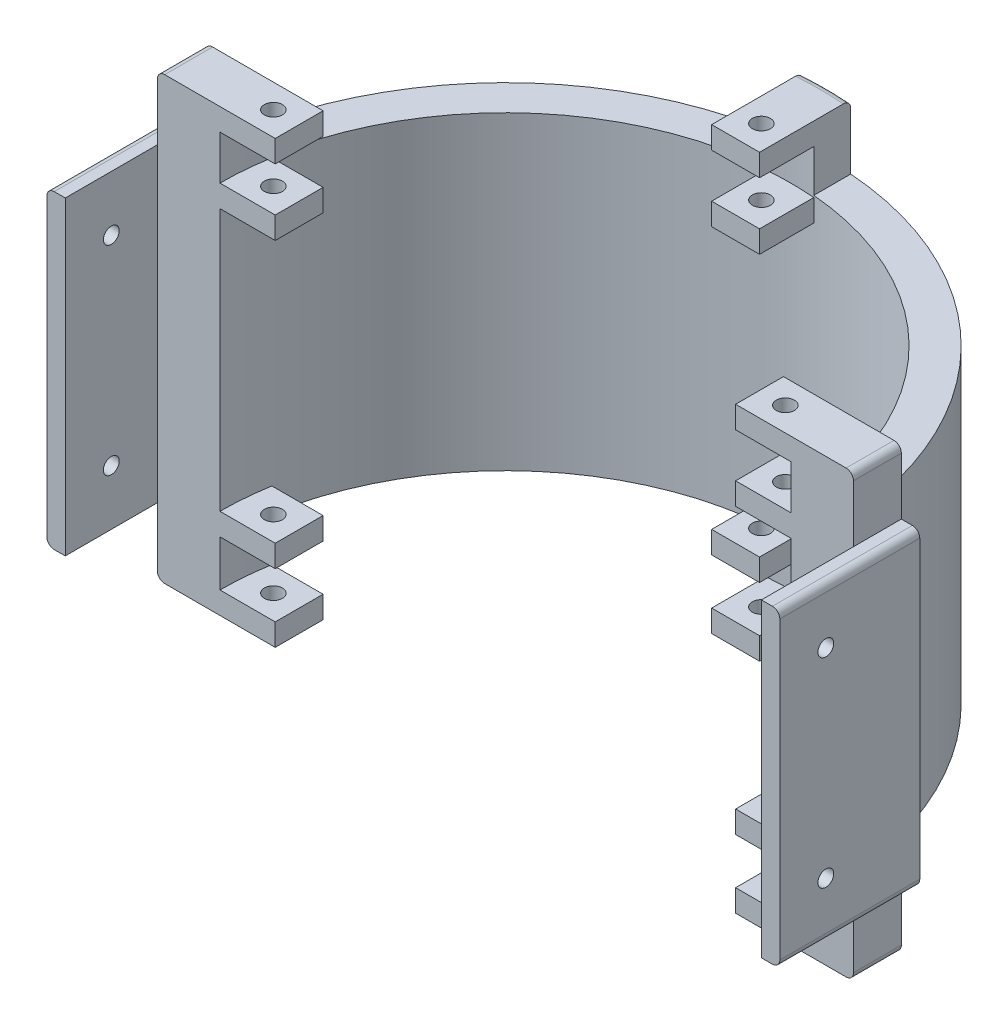
SolidWorks part; units mm, degrees
ref_plane "Front Plane" through (0, 0, 0) normal (0, 0, 1) x (1, 0, 0)
ref_plane "Top Plane" through (0, 0, 0) normal (0, 1, 0) x (1, 0, 0)
ref_plane "Right Plane" through (0, 0, 0) normal (1, 0, 0) x (0, 0, -1)
sketch "Sketch1" plane through (0, 0, 0) normal (0, 1, 0) x (1, 0, 0)
  line L0 (-148.0369, 0) -> (-77.5, 0) construction
  line L1 (-86.5289, 13) -> (-99.5, 13)
  line L2 (-99.5, 13) -> (-99.5, -25)
  line L3 (-99.5, -25) -> (-94.5, -25)
  line L4 (-94.5, -25) -> (-94.5, 0)
  line L5 (-94.5, 0) -> (-77.5, 0)
  line L7 (99.5, -25) -> (99.5, 13)
  line L8 (-65.0144, 0) -> (144.5537, 0) construction
  line L9 (99.5, 13) -> (86.5289, 13)
  line L10 (77.5, 0) -> (94.5, 0)
  line L11 (94.5, 0) -> (94.5, -25)
  line L12 (94.5, -25) -> (99.5, -25)
  arc A0 (77.5, 0) -> (-77.5, 0) centre (0, 0) ccw
  arc A1 (-86.5289, 13) -> (86.5289, 13) centre (0, 0) cw
  dimension "D1" = 155
  dimension "D4" = 10
  dimension "D2" = 25
  dimension "D3" = 25
  dimension "D5" = 17
  dimension "D6" = 17
  dimension "D7" = 5
  dimension "D8" = 5
  dimension "D9" = 13
  dimension "D10" = 13
extrude "Boss-Extrude1" add sketch "Sketch1" along normal blind 84.17
sketch "Sketch3" plane through (0, 84.17, 0) normal (0, 1, 0) x (1, 0, 0)
  line L0 (-94.5, 0) -> (-62.5, 0)
  line L1 (-94.5, 0) -> (-77.5, 0) construction
  line L2 (-62.5, 0) -> (-62.5, 13)
  line L3 (-62.5, 13) -> (-94.5, 13)
  line L5 (-94.5, 13) -> (-94.5, 0)
  line L6 (94.5, 0) -> (62.5, 0)
  line L7 (77.5, 0) -> (94.5, 0) construction
  line L8 (62.5, 0) -> (62.5, 13)
  line L9 (62.5, 13) -> (94.5, 13)
  line L11 (94.5, 13) -> (94.5, 0)
  line L12 (-94.5, -25) -> (-94.5, 0) construction
  line L13 (94.5, 0) -> (94.5, -25) construction
  dimension "D1" = 32
  dimension "D2" = 32
extrude "Boss-Extrude2" add sketch "Sketch3" against normal blind 6 from offset 0.5 offset against normal yes
sketch "Sketch4" plane through (0, 84.17, 0) normal (0, 1, 0) x (1, 0, 0)
  line L0 (-94.5, 13) -> (-76.4019, 13)
  line L1 (-94.5, 0) -> (-77.5, 0)
  line L2 (76.4019, 13) -> (94.5, 13)
  line L3 (94.5, 0) -> (77.5, 0)
  line L4 (-94.5, 0) -> (-94.5, 13)
  line L5 (99.5, 13) -> (86.5289, 13) construction
  line L6 (77.5, 0) -> (94.5, 0) construction
  line L7 (94.5, 13) -> (94.5, 0)
  line L8 (-94.5, -25) -> (-94.5, 0) construction
  line L9 (94.5, 0) -> (94.5, -25) construction
  arc A6 (-76.4019, 13) -> (-77.5, 0) centre (0, 0) ccw
  arc A7 (77.5, 0) -> (76.4019, 13) centre (0, 0) ccw
extrude "Boss-Extrude3" add sketch "Sketch4" along normal blind 11.5
sketch "Sketch5" plane through (0, 95.67, 0) normal (0, 1, 0) x (1, 0, 0)
  line L1 (-94.5, 0) -> (-62.5, 0)
  line L2 (-94.5, 0) -> (-94.5, 13)
  line L3 (-94.5, 13) -> (-62.5, 13)
  line L4 (-62.5, 0) -> (-62.5, 13)
  line L5 (94.5, 13) -> (62.5, 13)
  line L6 (94.5, 13) -> (94.5, 0)
  line L7 (94.5, 0) -> (62.5, 0)
  line L8 (62.5, 13) -> (62.5, 0)
extrude "Boss-Extrude4" add sketch "Sketch5" along normal blind 6
sketch "Sketch7" plane through (-99.5, 0, 0) normal (-1, 0, 0) x (0, 0, 1)
  line L0 (-13, 84.17) -> (25, 84.17) construction
  line L1 (-13, 0) -> (25, 0) construction
  line L2 (25, 84.17) -> (25, 0) construction
  circle A0 centre (12.5, 69.17) radius 2.15
  circle A1 centre (12.5, 15) radius 2.15
  dimension "D1" = 4.3
  dimension "D2" = 4.3
  dimension "D3" = 15
  dimension "D4" = 15
  dimension "D5" = 12.5
  dimension "D6" = 12.5
extrude "Cut-Extrude1" cut sketch "Sketch7" against normal through all
sketch "Sketch9" plane through (0, 0, 0) normal (0, -1, 0) x (1, 0, 0)
  line L0 (-86.5289, -13) -> (-99.5, -13) construction
  line L1 (-93.0144, -13) -> (-62.5, -13)
  line L2 (-93.0144, -13) -> (-93.0144, 0)
  line L3 (-93.0144, 0) -> (-62.5, 0)
  line L4 (-62.5, -13) -> (-62.5, 0)
  line L5 (99.5, -13) -> (86.5289, -13) construction
  line L6 (93.0144, -13) -> (62.5, -13)
  line L7 (93.0144, -13) -> (93.0144, 0)
  line L8 (93.0144, 0) -> (62.5, 0)
  line L9 (62.5, -13) -> (62.5, 0)
extrude "Boss-Extrude5" add sketch "Sketch9" against normal blind 6 from offset 0.5 offset against normal yes
sketch "Sketch11" plane through (0, 0, 0) normal (0, -1, 0) x (1, 0, 0)
  line L1 (-94.5, 0) -> (-77.5, 0)
  line L2 (-94.5, 0) -> (-94.5, -13)
  line L3 (-94.5, -13) -> (-76.4019, -13)
  line L6 (94.5, 0) -> (77.5, 0)
  line L7 (94.5, 0) -> (94.5, -13)
  line L8 (94.5, -13) -> (76.4019, -13)
  arc A0 (-77.5, 0) -> (-76.4019, -13) centre (0, 0) ccw
  arc A1 (76.4019, -13) -> (77.5, 0) centre (0, 0) ccw
extrude "Boss-Extrude6" add sketch "Sketch11" along normal blind 12
sketch "Sketch12" plane through (0, -12, 0) normal (0, -1, 0) x (1, 0, 0)
  line L1 (-94.5, -13) -> (-62.5, -13)
  line L2 (-94.5, -13) -> (-94.5, 0)
  line L3 (-94.5, 0) -> (-62.5, 0)
  line L4 (-62.5, -13) -> (-62.5, 0)
  line L5 (94.5, -13) -> (62.5, -13)
  line L6 (94.5, -13) -> (94.5, 0)
  line L7 (94.5, 0) -> (62.5, 0)
  line L8 (62.5, -13) -> (62.5, 0)
extrude "Boss-Extrude7" add sketch "Sketch12" along normal blind 6
sketch "Sketch14" plane through (0, 101.67, 0) normal (0, 1, 0) x (1, 0, 0)
  line L0 (-62.5, 0) -> (-62.5, 13) construction
  line L1 (62.5, 13) -> (62.5, 0) construction
  line L2 (-62.5, 13) -> (-94.5, 13) construction
  line L3 (94.5, 13) -> (62.5, 13) construction
  circle A0 centre (-69.5, 6.5) radius 2.45
  circle A1 centre (69.5, 6.5) radius 2.45
  dimension "D1" = 4.9
  dimension "D2" = 4.9
  dimension "D3" = 7
  dimension "D4" = 7
  dimension "D5" = 6.5
  dimension "D6" = 6.5
extrude "Cut-Extrude2" cut sketch "Sketch14" against normal through all
sketch "Sketch15" plane through (0, 84.17, 0) normal (0, 1, 0) x (1, 0, 0)
  line L2 (-6.5, 87.2582) -> (-6.5, 62.5)
  line L3 (-6.5, 62.5) -> (6.5, 62.5)
  line L4 (6.5, 87.2582) -> (6.5, 62.5)
  line L5 (-2.4417, 87.4659) -> (6.5, 62.5) construction
  line L6 (-6.5, 62.5) -> (2.4417, 87.4659) construction
  arc A0 (6.5, 77.2269) -> (-6.5, 77.2269) centre (0, 0) ccw
  arc A1 (6.5, 87.2582) -> (-6.5, 87.2582) centre (0, 0) ccw
  point P4 (0, 80.6486)
  dimension "D2" = 62.5
  dimension "D1" = 13
extrude "Boss-Extrude8" add sketch "Sketch15" against normal blind 6 from offset 0.5 contours L4 L3 L2 L6 | L4 L6 L2 L3 region at (-4.7064, 84.17, -72.4272) region at (1.2125, 84.17, -69.3178) offset against normal yes
sketch "Sketch17" plane through (0, 84.17, 0) normal (0, 1, 0) x (1, 0, 0)
  line L0 (-6.5, 77.2269) -> (-6.5, 87.2582)
  line L1 (6.5, 77.2269) -> (6.5, 87.2582)
  arc A0 (6.5, 87.2582) -> (-6.5, 87.2582) centre (0, 0) ccw
  arc A2 (6.5, 77.2269) -> (-6.5, 77.2269) centre (0, 0) ccw
extrude "Boss-Extrude9" add sketch "Sketch17" along normal blind 11.5
sketch "Sketch18" plane through (0, 95.67, 0) normal (0, 1, 0) x (1, 0, 0)
  line L0 (-6.5, 87.2582) -> (-6.5, 62.5)
  line L1 (-6.5, 62.5) -> (6.5, 62.5)
  line L2 (6.5, 62.5) -> (6.5, 87.2582)
  arc A0 (6.5, 87.2582) -> (-6.5, 87.2582) centre (0, 0) ccw
extrude "Boss-Extrude10" add sketch "Sketch18" along normal blind 6
sketch "Sketch20" plane through (0, 0, 0) normal (0, -1, 0) x (1, 0, 0)
  line L0 (-6.5, -62.5) -> (6.5, -62.5)
  line L1 (6.5, -62.5) -> (6.5, -87.2582)
  line L2 (-6.5, -62.5) -> (-6.5, -87.2582)
  arc A0 (-6.5, -87.2582) -> (6.5, -87.2582) centre (0, 0) ccw
extrude "Boss-Extrude11" add sketch "Sketch20" against normal blind 6 from offset 0.5 offset against normal yes
sketch "Sketch21" plane through (0, 0, 0) normal (0, -1, 0) x (1, 0, 0)
  line L0 (-6.5, -77.2269) -> (-6.5, -87.2582)
  line L1 (6.5, -77.2269) -> (6.5, -87.2582)
  arc A0 (-6.5, -87.2582) -> (6.5, -87.2582) centre (0, 0) ccw
  arc A2 (-6.5, -77.2269) -> (6.5, -77.2269) centre (0, 0) ccw
extrude "Boss-Extrude12" add sketch "Sketch21" along normal blind 12
sketch "Sketch22" plane through (0, -12, 0) normal (0, -1, 0) x (1, 0, 0)
  line L0 (-6.5, -87.2582) -> (-6.5, -62.5)
  line L1 (-6.5, -62.5) -> (6.5, -62.5)
  line L2 (6.5, -62.5) -> (6.5, -87.2582)
  arc A0 (-6.5, -87.2582) -> (6.5, -87.2582) centre (0, 0) ccw
extrude "Boss-Extrude13" add sketch "Sketch22" along normal blind 6
sketch "Sketch19" plane through (0, 101.67, 0) normal (0, 1, 0) x (1, 0, 0)
  line L0 (-6.5, 87.2582) -> (-6.5, 62.5) construction
  line L1 (-6.5, 62.5) -> (6.5, 62.5) construction
  circle A0 centre (0, 69.5) radius 2.45
  dimension "D1" = 4.9
  dimension "D2" = 6.5
  dimension "D3" = 7
extrude "Cut-Extrude3" cut sketch "Sketch19" against normal through all
fillet "Fillet4" radius 2 10 edges at (99.5, 0, 6) (94.5, -18, -6.5) (0, -18, -87.5) (-99.5, 0, 6) (-94.5, -18, -6.5) (-99.5, 84.17, 6) (99.5, 84.17, 6) (94.5, 101.67, -6.5) (0, 101.67, -87.5) (-94.5, 101.67, -6.5)
fillet "Fillet5" radius 4 2 edges at (-86.5289, 42.085, -13) (86.5289, 42.085, -13)
equation "\"D6@Sketch7\"=\"D5@Sketch7\""
equation "\"D2@Sketch14\"=\"D1@Sketch14\""
